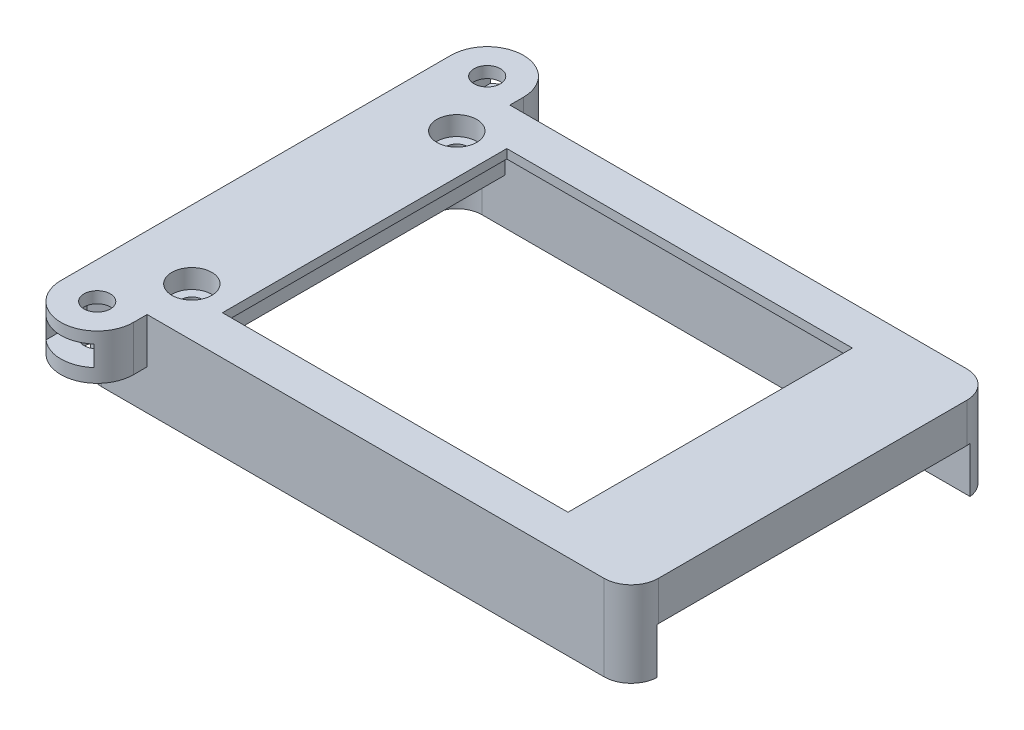
SolidWorks part; units mm, degrees
ref_plane "Front Plane" through (0, 0, 0) normal (0, 0, 1) x (1, 0, 0)
ref_plane "Top Plane" through (0, 0, 0) normal (0, 1, 0) x (1, 0, 0)
ref_plane "Right Plane" through (0, 0, 0) normal (1, 0, 0) x (0, 0, -1)
sketch "Sketch1" plane through (0, 0, 0) normal (0, 0, 1) x (1, 0, 0)
  line L0 (-23.495, -2.8321) -> (-20.447, -2.8321) construction
  line L1 (-20.447, 0) -> (-20.447, -2.8321) construction
  line L2 (-23.495, -2.8321) -> (-26.035, -2.8321) construction
  line L3 (-26.035, -2.8321) -> (-26.035, -4.4196) construction
  line L4 (-23.495, -2.8321) -> (-20.447, -2.8321) construction
  line L5 (-20.447, 0) -> (-20.447, -2.8321) construction
  line L6 (-23.495, -2.8321) -> (-26.035, -2.8321) construction
  line L7 (-26.035, -2.8321) -> (-26.035, -4.4196) construction
  line L8 (-9.4742, -6.2992) -> (-26.035, -6.2992) construction
  line L9 (-26.035, -6.2992) -> (-26.035, -4.4196) construction
  line L10 (-9.4742, -6.2992) -> (-26.035, -6.2992) construction
  line L11 (-26.035, -6.2992) -> (-26.035, -4.4196) construction
  line L12 (-20.947, 1.5) -> (-20.947, -2.8321)
  line L13 (-20.947, -2.8321) -> (-26.035, -2.8321)
  line L14 (-26.035, -2.8321) -> (-26.035, -7.9085)
  line L15 (-28.6272, -8.4085) -> (-21.9464, -8.4085) construction
  line L16 (-28.6272, -8.4085) -> (-21.9464, -8.4085) construction
  line L17 (-26.035, -7.9085) -> (-31.035, -7.9085)
  line L18 (-31.035, -7.9085) -> (-31.035, 1.5)
  line L19 (-31.035, 1.5) -> (-20.947, 1.5)
  line L20 (-20.447, 0) -> (26.0604, 0) construction
  line L21 (-20.447, 0) -> (26.0604, 0) construction
  dimension "D1" = 1
  dimension "D2" = 0.5
  dimension "D3" = 1.5
  dimension "D4" = 5
extrude "Boss-Extrude1" add sketch "Sketch1" along normal mid plane 40
sketch "Sketch2" plane through (0, 1.5, 0) normal (0, 1, 0) x (1, 0, 0)
  line L0 (-24.6493, -17.145) -> (-20.947, -17.145)
  line L1 (-20.947, -20) -> (-20.947, 20) construction
  line L2 (-20.947, -17.145) -> (-20.947, -20)
  line L3 (-20.947, -20) -> (-26.035, -20)
  line L4 (-20.947, -20) -> (-31.035, -20) construction
  line L5 (-26.035, -20) -> (-26.035, -17.145)
  line L6 (-26.035, -20) -> (-26.035, 20) construction
  line L7 (-26.035, -17.145) -> (-26.035, -15.7593)
  line L8 (-23.495, 17.395) -> (-23.495, 20)
  line L9 (-20.947, 20) -> (-31.035, 20) construction
  line L10 (-23.495, 20) -> (-26.035, 20)
  line L11 (-26.035, 20) -> (-26.035, 15.7593)
  arc A0 (-26.035, -14.605) -> (-23.495, -17.145) centre (-23.495, -14.605) ccw construction
  arc A1 (-26.035, -14.605) -> (-23.495, -17.145) centre (-23.495, -14.605) ccw construction
  arc A2 (-23.495, 17.145) -> (-26.035, 14.605) centre (-23.495, 14.605) ccw construction
  arc A3 (-23.495, 17.145) -> (-26.035, 14.605) centre (-23.495, 14.605) ccw construction
  arc A4 (-26.035, -15.7593) -> (-24.6493, -17.145) centre (-23.495, -14.605) ccw
  arc A5 (-26.285, -14.605) -> (-23.495, -17.395) centre (-23.495, -14.605) ccw construction
  arc A6 (-23.495, 17.395) -> (-26.035, 15.7593) centre (-23.495, 14.605) ccw
  arc A7 (-23.495, 17.395) -> (-26.285, 14.605) centre (-23.495, 14.605) ccw construction
  dimension "D1" = 0.25
  dimension "D2" = 0.25
extrude "Boss-Extrude2" add sketch "Sketch2" against normal up to surface (9.4085 mm away) up to face at (-28.535, -7.9085, 0)
fillet "Fillet1" radius 3 2 edges at (-31.035, -3.2043, -20) (-31.035, -3.2043, 20)
sketch "Sketch5" plane through (0, 1.5, 0) normal (0, 1, 0) x (1, 0, 0)
  line L0 (-20.947, 20) -> (27.345, 20)
  line L1 (-20.947, -20) -> (27.345, -20)
  line L2 (30.345, -17) -> (30.345, 17)
  line L3 (-20.947, -20) -> (-20.947, 20) construction
  line L4 (-20.947, -20) -> (-20.947, 20)
  line L5 (29.845, -14.605) -> (29.845, 14.605) construction
  line L8 (19.05, 15.6781) -> (19.05, -15.6781) construction
  line L9 (19.05, -15.6781) -> (-19.05, -15.6781) construction
  line L10 (19.05, 15.6781) -> (-19.05, 15.6781) construction
  line L11 (-19.05, 15.6781) -> (-19.05, -15.6781) construction
  line L12 (19.05, 15.6781) -> (19.05, -15.6781)
  line L13 (19.05, -15.6781) -> (-19.05, -15.6781)
  line L14 (19.05, 15.6781) -> (-19.05, 15.6781)
  line L15 (-19.05, 15.6781) -> (-19.05, -15.6781)
  arc A0 (27.345, -20) -> (30.345, -17) centre (27.345, -17) ccw
  arc A1 (30.345, 17) -> (27.345, 20) centre (27.345, 17) ccw
  arc A2 (-31.035, -17) -> (-28.035, -20) centre (-28.035, -17) ccw construction
  dimension "D1" = 0.5
extrude "Boss-Extrude5" add sketch "Sketch5" against normal offset from surface (1 mm away) 0.5
sketch "Sketch6" plane through (0, 0.5, 0) normal (0, -1, 0) x (1, 0, 0)
  line L0 (-23.495, 17.145) -> (27.305, 17.145) construction
  line L1 (-20.947, 17.145) -> (26.8104, 17.145)
  line L2 (26.0604, -17.145) -> (-20.447, -17.145) construction
  line L3 (-20.947, 20) -> (-20.947, -20) construction
  line L4 (-20.947, 20) -> (-20.947, 17.145)
  line L5 (27.345, 20) -> (-20.947, 20) construction
  line L6 (27.345, 20) -> (-20.947, 20)
  line L7 (-20.947, -20) -> (27.345, -20) construction
  line L8 (30.345, -17) -> (30.345, 17) construction
  line L9 (-20.947, -20) -> (27.345, -20)
  line L10 (30.345, -17) -> (30.345, 17)
  line L11 (26.0604, 17.145) -> (26.0604, 14.4018) construction
  line L12 (26.0604, 17.145) -> (26.0604, 14.4018) construction
  line L13 (26.8104, 17.145) -> (26.8104, -17.395)
  line L14 (26.0604, -17.145) -> (-20.447, -17.145) construction
  line L15 (-20.947, -20) -> (-20.947, -17.395)
  line L16 (-20.947, -17.395) -> (26.8104, -17.395)
  arc A4 (30.345, 17) -> (27.345, 20) centre (27.345, 17) ccw construction
  arc A5 (30.345, 17) -> (27.345, 20) centre (27.345, 17) ccw
  arc A6 (27.345, -20) -> (30.345, -17) centre (27.345, -17) ccw construction
  arc A7 (27.345, -20) -> (30.345, -17) centre (27.345, -17) ccw
  dimension "D2" = 1.5
  dimension "D1" = 0.25
extrude "Boss-Extrude6" add sketch "Sketch6" along normal up to surface (3.3321 mm away)
sketch "Sketch7" plane through (0, -2.8321, 0) normal (0, -1, 0) x (1, 0, 0)
  line L1 (-20.947, 20) -> (27.345, 20)
  line L2 (-20.947, 20) -> (-20.947, 17.145)
  line L3 (-20.947, 17.145) -> (30.3415, 17.145)
  line L6 (-23.495, -20) -> (27.345, -20)
  line L7 (-23.495, -20) -> (-23.495, -17.395)
  line L8 (-23.495, -17.395) -> (30.3189, -17.395)
  arc A0 (30.345, 17) -> (27.345, 20) centre (27.345, 17) ccw construction
  arc A1 (27.345, -20) -> (30.345, -17) centre (27.345, -17) ccw construction
  arc A2 (30.3415, 17.145) -> (27.345, 20) centre (27.345, 17) ccw
  arc A3 (27.345, -20) -> (30.3189, -17.395) centre (27.345, -17) ccw
extrude "Boss-Extrude7" add sketch "Sketch7" along normal up to surface (5.0764 mm away) up to face at (-25.9411, -7.9085, 1.5134)
sketch "Sketch9" plane through (0, 1.5, 0) normal (0, 1, 0) x (1, 0, 0)
  line L0 (-31.035, 17) -> (-31.035, 21.5)
  line L1 (-23.035, 21.5) -> (-23.035, 20)
  line L2 (27.345, 20) -> (-28.035, 20) construction
  line L3 (-23.035, 20) -> (-28.035, 20)
  line L4 (0, 0) -> (-7.0217, 0) construction
  line L5 (-23.035, -20) -> (-28.035, -20)
  line L6 (-23.035, -21.5) -> (-23.035, -20)
  line L7 (-31.035, -17) -> (-31.035, -21.5)
  arc A0 (-31.035, 21.5) -> (-23.035, 21.5) centre (-27.035, 21.5) cw
  arc A1 (-28.035, 20) -> (-31.035, 17) centre (-28.035, 17) ccw
  arc A2 (-28.035, -20) -> (-31.035, -17) centre (-28.035, -17) cw
  arc A3 (-31.035, -21.5) -> (-23.035, -21.5) centre (-27.035, -21.5) ccw
  dimension "D1" = 8
  dimension "D2" = 1.5
extrude "Boss-Extrude8" add sketch "Sketch9" against normal blind 5
hole_wizard "M2.5 Clearance Hole1" positions "Sketch10" profile "Sketch11" hole size "M2.5" standard "ANSI Metric" end condition through all
sketch "Sketch10" plane through (0, 1.5, 0) normal (0, 1, 0) x (1, 0, 0)
  point P0 (-27.035, -21.5)
  point P3 (-27.035, 21.5)
sketch "Sketch11" plane through (-27.035, 1.5, 21.5) normal (1, 0, 0) x (0, 0, 1)
  line L0 (0, 0) -> (0, 9.4085)
  line L1 (0, 9.4085) -> (1.45, 9.4085)
  line L2 (1.45, 9.4085) -> (1.45, 0)
  line L5 (1.45, 0) -> (0, 0)
  line L11 (0, -6.35) -> (0, 107.95) construction
  dimension "Thru Hole Dia." = 2.9
  dimension "Thru Hole Depth" = 9.4085
ref_plane "Plane1" through (0, -2, 0) normal (0, 1, 0) x (1, 0, 0)
sketch "Sketch12" plane through (0, -2, 0) normal (0, 1, 0) x (1, 0, 0)
  line L0 (-29.685, -23.03) -> (-29.685, -29.56)
  line L1 (-24.385, -23.03) -> (-24.385, -19.97)
  line L2 (-24.385, -19.97) -> (-27.035, -18.44)
  line L3 (-27.035, -18.44) -> (-29.685, -19.97)
  line L4 (-29.685, -19.97) -> (-29.685, -23.03)
  line L5 (-29.685, -23.03) -> (-27.035, -24.56) construction
  line L6 (-27.035, -24.56) -> (-24.385, -23.03) construction
  line L13 (-29.685, -29.56) -> (-24.385, -29.56)
  line L14 (-24.385, -29.56) -> (-24.385, -23.03)
  line L15 (0, 0) -> (-12.2155, 0) construction
  line L16 (-29.685, 23.03) -> (-29.685, 29.56)
  line L17 (-29.685, 29.56) -> (-24.385, 29.56)
  line L18 (-24.385, 29.56) -> (-24.385, 23.03)
  line L19 (-24.385, 23.03) -> (-24.385, 19.97)
  line L20 (-24.385, 19.97) -> (-27.035, 18.44)
  line L21 (-27.035, 18.44) -> (-29.685, 19.97)
  line L22 (-29.685, 19.97) -> (-29.685, 23.03)
  circle A0 centre (-27.035, -21.5) radius 2.65 construction
  circle A2 centre (-27.035, -21.5) radius 2.5 construction
  dimension "D1" = 5
  dimension "D2" = 0.15
  dimension "D3" = 5
extrude "Cut-Extrude1" cut sketch "Sketch12" along normal blind 2.25
sketch "Sketch13" plane through (0, 1.5, 0) normal (0, 1, 0) x (1, 0, 0)
  circle A0 centre (-23.495, 14.605) radius 1.016 construction
  circle A1 centre (-23.495, -14.605) radius 1.016 construction
  circle A2 centre (27.305, -14.605) radius 1.016 construction
  circle A3 centre (27.305, 14.605) radius 1.016 construction
  circle A4 centre (-23.495, 14.605) radius 1.016
  circle A5 centre (-23.495, -14.605) radius 1.016
  circle A6 centre (27.305, -14.605) radius 1.016
  circle A7 centre (27.305, 14.605) radius 1.016
hole_wizard "CBORE for M2 SHCS1" positions "Sketch14" profile "Sketch15" counterbore size "M2" standard "ANSI Metric" end condition through all
sketch "Sketch14" plane through (0, 1.5, 0) normal (0, 1, 0) x (1, 0, 0)
  point P0 (-23.495, -14.605)
  point P3 (-23.495, 14.605)
sketch "Sketch15" plane through (-23.495, 1.5, 14.605) normal (1, 0, 0) x (0, 0, 1)
  line L0 (0, 0) -> (0, 9.4085)
  line L1 (0, 9.4085) -> (1.2, 9.4085)
  line L3 (1.2, 9.4085) -> (1.2, 2.1)
  line L4 (1.2, 2.1) -> (2.2, 2.1)
  line L5 (2.2, 2.1) -> (2.2, 0)
  line L7 (2.2, 0) -> (0, 0)
  line L11 (0, -6.35) -> (0, 107.95) construction
  dimension "Thru Hole Dia." = 2.4
  dimension "Thru Hole Depth" = 9.4085
  dimension "C'Bore Dia." = 4.4
  dimension "C'Bore Depth" = 2.1
